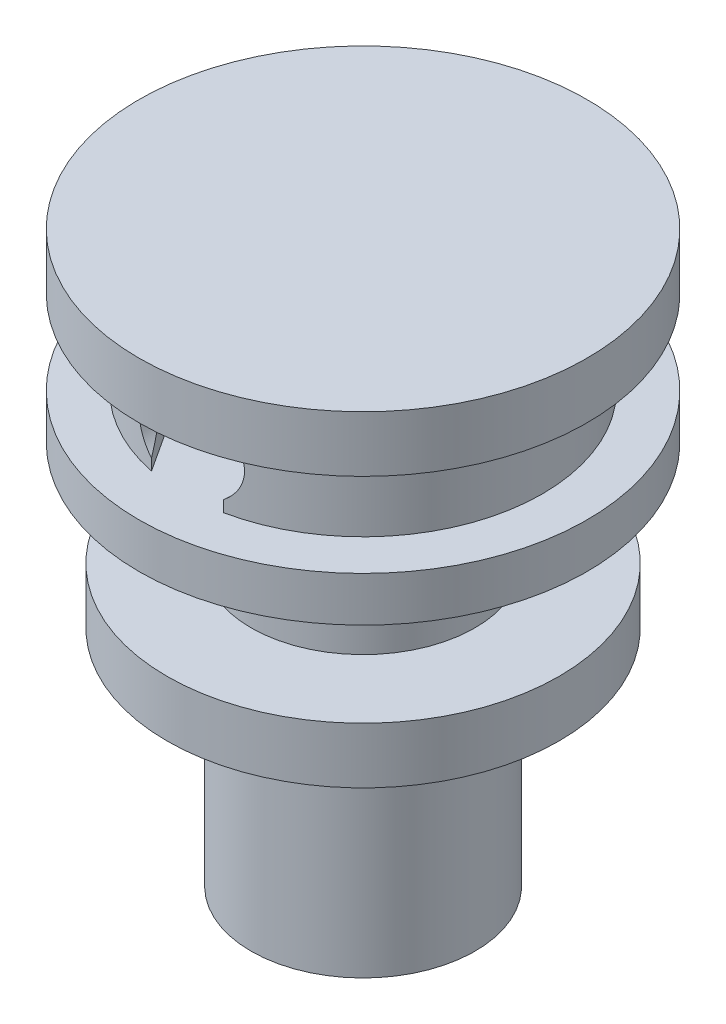
SolidWorks part; units mm, degrees
ref_plane "Alzado" through (0, 0, 0) normal (0, 0, 1) x (1, 0, 0)
ref_plane "Planta" through (0, 0, 0) normal (0, 1, 0) x (1, 0, 0)
ref_plane "Vista lateral" through (0, 0, 0) normal (1, 0, 0) x (0, 0, -1)
sketch "Croquis1" plane through (0, 0, 0) normal (0, 1, 0) x (1, 0, 0)
  circle A0 centre (0, 0) radius 1
  dimension "D1" = 2
extrude "Saliente-Extruir1" add sketch "Croquis1" along normal blind 2
sketch "Croquis2" plane through (0, 2, 0) normal (0, 1, 0) x (1, 0, 0)
  circle A0 centre (0, 0) radius 1.75
  dimension "D1" = 3.5
extrude "Saliente-Extruir2" add sketch "Croquis2" along normal blind 0.5
sketch "Croquis3" plane through (0, 2.5, 0) normal (0, 1, 0) x (1, 0, 0)
  circle A0 centre (0, 0) radius 1
  dimension "D1" = 2
extrude "Saliente-Extruir3" add sketch "Croquis3" along normal blind 0.935
sketch "Croquis4" plane through (0, 3.435, 0) normal (0, 1, 0) x (1, 0, 0)
  circle A0 centre (0, 0) radius 2
  dimension "D1" = 4
extrude "Saliente-Extruir4" add sketch "Croquis4" along normal blind 0.4
sketch "Croquis6" plane through (0, 3.835, 0) normal (0, 1, 0) x (1, 0, 0)
  circle A0 centre (0, 0) radius 1.6
  dimension "D1" = 3.2
extrude "Saliente-Extruir5" add sketch "Croquis6" along normal blind 0.75
sketch "Croquis7" plane through (0, 4.585, 0) normal (0, 1, 0) x (1, 0, 0)
  circle A0 centre (0, 0) radius 2
  dimension "D1" = 4
extrude "Saliente-Extruir6" add sketch "Croquis7" along normal blind 0.5
sketch "Croquis11" plane through (0, 0, 0) normal (0, 0, 1) x (1, 0, 0)
  line L0 (-1.6, 4.585) -> (-1.6, 3.835) construction
  line L1 (-1.6, 4.585) -> (-1.6, 3.835) construction
  line L2 (-1.6, 4.21) -> (1.6, 4.21) construction
  line L3 (1.6, 3.835) -> (1.6, 4.585) construction
  line L4 (1.6, 4.21) -> (0, 0) construction
  line L5 (0, 0) -> (0, 4.21) construction
  ellipse E0 centre (0, 4.21) end of major axis (-0.4711, 4.21) minor radius 0.375
extrude "Cortar-Extruir2" cut sketch "Croquis11" against normal blind 10 and the other way blind 10
sketch "Croquis12" plane through (0, 4.585, 0) normal (0, -1, 0) x (1, 0, 0)
  circle A0 centre (0, 0) radius 1
extrude "Cortar-Extruir3" cut sketch "Croquis12" along normal blind 0.75
sketch "Croquis13" plane through (0, 4.585, 0) normal (0, -1, 0) x (1, 0, 0)
  line L6 (0, 1.6) -> (0, -1.6) construction
  line L18 (-0.3, -1.6) -> (-0.9425, -0.6143)
  line L21 (0, -1.6) -> (0.3, -1.6)
  line L22 (0, -1.6) -> (-0.3, -1.6)
  line L26 (0.3, -1.6) -> (0.9425, -0.6143)
  line L27 (0.3, 1.6) -> (0, 1.6)
  line L28 (0, 1.6) -> (-0.3, 1.6)
  line L29 (0.3, 1.6) -> (0.9425, 0.6143)
  line L35 (-0.3, 1.6) -> (-0.9425, 0.6143)
  circle A0 centre (0, 0) radius 1 construction
  arc A3 (-0.9425, 0.6143) -> (-0.9425, -0.6143) centre (0, 0) ccw
  arc A4 (0.9425, -0.6143) -> (0.9425, 0.6143) centre (0, 0) ccw
  point P7 (0, 0)
  point P12 (0, 0)
  point P16 (0, 0)
  point P17 (0, 0)
  dimension "D3" = 2.25
  dimension "D1" = 1.6
  dimension "D2" = 0.6
extrude "Cortar-Extruir4" cut sketch "Croquis13" along normal blind 0.75
